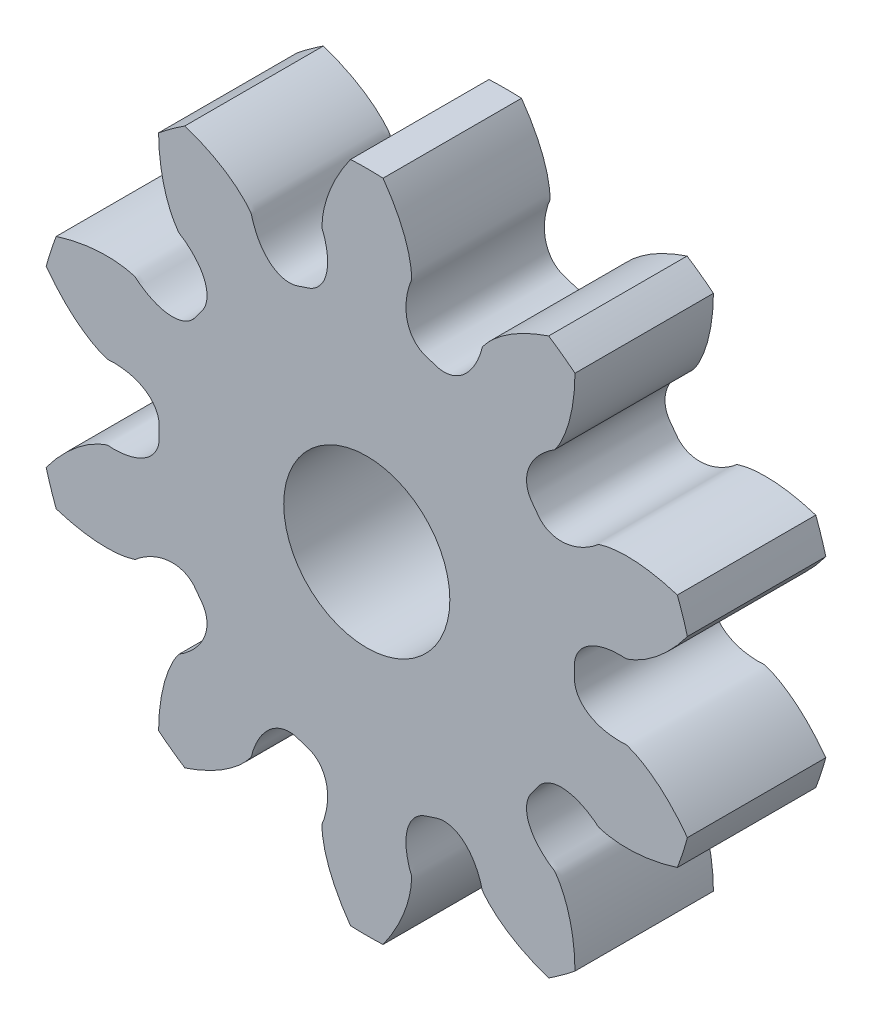
SolidWorks part; units mm, degrees
ref_plane "Front" through (0, 0, 0) normal (0, 0, 1) x (1, 0, 0)
ref_plane "Top" through (0, 0, 0) normal (0, 1, 0) x (1, 0, 0)
ref_plane "Right" through (0, 0, 0) normal (1, 0, 0) x (0, 0, -1)
ref_axis "Axis1" through (0, 0, 50) along (0, 0, -1)
sketch "SketchRevolvePlanet_Revolving_Follower01" plane through (0, 0, 0) normal (1, 0, 0) x (0, 0, -1)
  line L0 (0, 0) -> (1, 0) construction
  line L1 (-1.25, 0) -> (-1.25, 6)
  line L2 (-1.25, 6) -> (1.25, 6)
  line L3 (1.25, 6) -> (1.25, 0)
  line L4 (1.25, 0) -> (-1.25, 0)
  dimension "Side1" = 1.25
  dimension "OutsideRadius" = 6
  dimension "Side2" = 1.25
revolve "Planet_Revolving_Follower01" add sketch "SketchRevolvePlanet_Revolving_Follower01" angle 360 about L0
sketch "SketchToothPlanet_Revolving_Follower01" plane through (0, 0, 0) normal (0, 0, 1) x (1, 0, 0)
  arc A0 (5.8278, 1.6245) -> (5.8278, -1.6245) centre (0, 0) cw
  spline S0 degree 3 poles (5.8278, -1.6245) (5.7711, -1.5447) (5.6839, -1.4312) (5.5618, -1.2915) (5.474, -1.1989) (5.3881, -1.1154) (5.3046, -1.0405) (5.2242, -0.9741) (5.1472, -0.9156) (5.0743, -0.8647) (5.006, -0.8209) (4.9425, -0.7839) (4.8845, -0.7531) (4.8322, -0.7281) (4.7861, -0.7079) (4.7371, -0.69) (4.6757, -0.6643) (4.6071, -0.6779) (4.5448, -0.6755) (4.4956, -0.6739) (4.4475, -0.6702) (4.4006, -0.6651) (4.3549, -0.6584) (4.3103, -0.6501) (4.2669, -0.6403) (4.2246, -0.6289) (4.1835, -0.616) (4.1436, -0.6014) (4.1049, -0.5851) (4.0674, -0.5671) (4.031, -0.5472) (3.996, -0.5254) (3.9622, -0.5015) (3.9298, -0.4753) (3.899, -0.4468) (3.87, -0.4157) (3.843, -0.3818) (3.8184, -0.3451) (3.7967, -0.3055) (3.7783, -0.2632) (3.7639, -0.2183) (3.7539, -0.1713) (3.7497, -0.1283) (3.7482, -0.0711) (3.7513, 0) (3.7482, 0.0711) (3.7497, 0.1283) (3.7539, 0.1713) (3.7639, 0.2183) (3.7783, 0.2632) (3.7967, 0.3055) (3.8184, 0.3451) (3.843, 0.3818) (3.87, 0.4157) (3.899, 0.4468) (3.9298, 0.4753) (3.9622, 0.5015) (3.996, 0.5254) (4.031, 0.5472) (4.0674, 0.5671) (4.1049, 0.5851) (4.1436, 0.6014) (4.1835, 0.616) (4.2246, 0.6289) (4.2669, 0.6403) (4.3103, 0.6501) (4.3549, 0.6584) (4.4006, 0.6651) (4.4475, 0.6702) (4.4956, 0.6739) (4.5448, 0.6755) (4.6071, 0.6779) (4.6757, 0.6643) (4.7371, 0.69) (4.7861, 0.7079) (4.8322, 0.7281) (4.8845, 0.7531) (4.9425, 0.7839) (5.006, 0.8209) (5.0743, 0.8647) (5.1472, 0.9156) (5.2242, 0.9741) (5.3046, 1.0405) (5.3881, 1.1154) (5.474, 1.1989) (5.5618, 1.2915) (5.6839, 1.4312) (5.7711, 1.5447) (5.8278, 1.6245) knots 0 0 0 0 0.05171 0.075523 0.097976 0.119068 0.138799 0.15717 0.17418 0.189829 0.204117 0.217044 0.228611 0.238817 0.247662 0.255146 0.266488 0.281932 0.290791 0.299458 0.307939 0.316243 0.324379 0.332357 0.340187 0.347883 0.35546 0.362932 0.370318 0.37764 0.384918 0.392178 0.399448 0.406756 0.414133 0.42161 0.429217 0.436977 0.444912 0.453029 0.461324 0.469778 0.478358 0.484106 0.5 0.515894 0.521642 0.530222 0.538676 0.546971 0.555088 0.563023 0.570783 0.57839 0.585867 0.593244 0.600552 0.607822 0.615082 0.62236 0.629682 0.637068 0.64454 0.652117 0.659813 0.667643 0.675621 0.683757 0.692061 0.700542 0.709209 0.718068 0.733512 0.744854 0.752338 0.761183 0.771389 0.782956 0.795883 0.810171 0.82582 0.84283 0.861201 0.880932 0.902024 0.924477 0.94829 1 1 1 1
extrude "ToothExtrudeCutPlanet_Revolving_Follower01" cut sketch "SketchToothPlanet_Revolving_Follower01" against normal through all and the other way through all
pattern_circular "PatternPlanet_Revolving_Follower01" count 10 every 36 about axis through (0, 0, 50) along (0, 0, -1) of "ToothExtrudeCutPlanet_Revolving_Follower01"
sketch "BoreRevolveSketch" plane through (0, 0, 0) normal (1, 0, 0) x (0, 0, -1)
  line L0 (0, 0) -> (1, 0) construction
  line L1 (-1.75, 0) -> (1.75, 0)
  line L2 (1.75, 0) -> (1.75, 1.5)
  line L3 (1.75, 1.5) -> (-1.75, 1.5)
  line L4 (-1.75, 1.5) -> (-1.75, 0)
  dimension "BoreSide1" = 1.75
  dimension "TaperSide1" = 1.5
  dimension "BoreSide2" = 1.75
  dimension "TaperSide2" = 1.5
revolve "BoreRevolveCut" cut sketch "BoreRevolveSketch" angle 360 about L0
sketch "KeywaySketch" plane through (0, 0, 0) normal (0, 0, 1) x (1, 0, 0)
  line L0 (0, 0) -> (3, 0) construction
sketch "AuxiliarySketchPlanet_Revolving_Follower01" plane through (0, 0, 0) normal (0, 0, 1) x (1, 0, 0)
  circle A0 centre (0, 0) radius 5 construction
  circle A1 centre (0, 0) radius 4.6985 construction
  circle A2 centre (0, 0) radius 4.8934 construction
  circle A3 centre (0, 0) radius 6 construction
  circle A4 centre (0, 0) radius 3.75 construction
  dimension "PitchDiameter" = 10
  dimension "BaseDiameter" = 9.3969
  dimension "FormDiameter" = 9.7869
  dimension "MajorDiameter" = 12
  dimension "MinorDiameter" = 7.5
